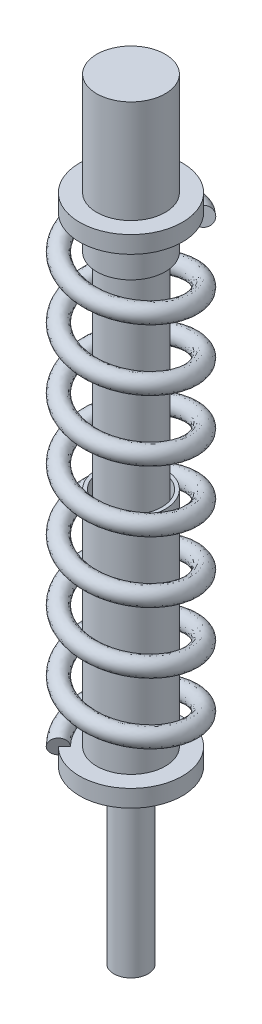
SolidWorks part; units mm, degrees
ref_plane "Front Plane" through (0, 0, 0) normal (0, 0, 1) x (1, 0, 0)
ref_plane "Top Plane" through (0, 0, 0) normal (0, 1, 0) x (1, 0, 0)
ref_plane "Right Plane" through (0, 0, 0) normal (1, 0, 0) x (0, 0, -1)
sketch "Sketch1" plane through (0, 0, 0) normal (0, 1, 0) x (1, 0, 0)
  circle A0 centre (0, 0) radius 5
  dimension "D1" = 10
extrude "Boss-Extrude1" add sketch "Sketch1" along normal blind 50
sketch "Sketch2" plane through (0, 50, 0) normal (0, 1, 0) x (1, 0, 0)
  circle A0 centre (0, 0) radius 15
  dimension "D1" = 30
extrude "Boss-Extrude2" add sketch "Sketch2" along normal blind 5
sketch "Sketch3" plane through (0, 55, 0) normal (0, 1, 0) x (1, 0, 0)
  circle A0 centre (0, 0) radius 10
  dimension "D1" = 20
extrude "Boss-Extrude3" add sketch "Sketch3" along normal blind 65
sketch "Sketch4" plane through (0, 120, 0) normal (0, 1, 0) x (1, 0, 0)
  circle A0 centre (0, 0) radius 9
  dimension "D1" = 18
extrude "Cut-Extrude1" cut sketch "Sketch4" against normal blind 60
sketch "Sketch5" plane through (0, 60, 0) normal (0, 1, 0) x (1, 0, 0)
  circle A0 centre (0, 0) radius 8
  dimension "D1" = 16
extrude "Boss-Extrude4" add sketch "Sketch5" along normal blind 120
sketch "Sketch6" plane through (0, 180, 0) normal (0, 1, 0) x (1, 0, 0)
  circle A0 centre (0, 0) radius 10
extrude "Boss-Extrude5" add sketch "Sketch6" along normal blind 10
sketch "Sketch7" plane through (0, 190, 0) normal (0, 1, 0) x (1, 0, 0)
  circle A0 centre (0, 0) radius 15
extrude "Boss-Extrude6" add sketch "Sketch7" along normal blind 5
sketch "Sketch8" plane through (0, 195, 0) normal (0, 1, 0) x (1, 0, 0)
  circle A0 centre (0, 0) radius 10
  dimension "D1" = 20
extrude "Boss-Extrude7" add sketch "Sketch8" along normal blind 30
sketch "Sketch9" plane through (0, 55, 0) normal (0, 1, 0) x (1, 0, 0)
  circle A0 centre (0, 0) radius 15
curve "Helix/Spiral1" pitch 17.8667 height 134 turns 7.5
sweep "Sweep1" add path "Helix/Spiral1" circular profile diameter 5 parameters "D3"=5
